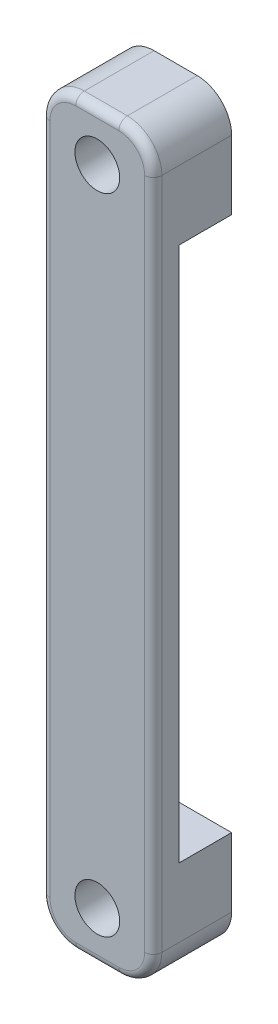
SolidWorks part; units mm, degrees
material "ABS"
ref_plane "Front Plane" through (0, 0, 0) normal (0, 0, 1) x (1, 0, 0)
ref_plane "Top Plane" through (0, 0, 0) normal (0, 1, 0) x (1, 0, 0)
ref_plane "Right Plane" through (0, 0, 0) normal (1, 0, 0) x (0, 0, -1)
sketch "Sketch1" plane through (0, 0, 0) normal (0, 0, 1) x (1, 0, 0)
  line L0 (-64.1444, 69.4911) -> (92.8306, 69.4911) construction
  line L1 (7.3028, 69.4911) -> (-5.6972, 69.4911)
  line L2 (7.3028, 69.4911) -> (7.3028, -18.6589)
  line L3 (7.3028, -18.6589) -> (-5.6972, -18.6589)
  line L4 (-5.6972, 69.4911) -> (-5.6972, -18.6589)
  line L5 (-5.6972, 68.4911) -> (7.3028, 68.4911)
  line L6 (-5.6972, -17.6589) -> (7.3028, -17.6589)
  line L7 (92.8306, -18.6589) -> (-64.1444, -18.6589) construction
  circle A0 centre (0.8028, 32.3036) radius 2.5 construction
  dimension "D1" = 4
  dimension "D2" = 4
  dimension "D3" = 1
  dimension "D4" = 1
extrude "Boss-Extrude1" add sketch "Sketch1" along normal blind 3 contours L4 L6 L2 L5 region at (0.8028, 25.4161, 0)
sketch "Sketch2" plane through (0, 0, 0) normal (0, 0, -1) x (-1, 0, 0)
  line L5 (-7.3028, 68.4911) -> (-7.3028, 56.4911)
  line L24 (-7.3028, 68.4911) -> (5.6972, 68.4911)
  line L25 (-7.3028, 56.4911) -> (5.6972, 56.4911)
  line L26 (5.6972, 68.4911) -> (5.6972, 56.4911)
  line L27 (-7.3028, 68.4911) -> (-7.3028, -17.6589) construction
  line L28 (5.6972, 68.4911) -> (5.6972, -17.6589) construction
  line L29 (-7.3028, 25.4161) -> (5.6972, 25.4161)
  line L30 (5.6972, -17.6589) -> (5.6972, -5.6589)
  line L31 (-7.3028, -5.6589) -> (5.6972, -5.6589)
  line L32 (-7.3028, -17.6589) -> (5.6972, -17.6589)
  line L33 (-7.3028, -17.6589) -> (-7.3028, -5.6589)
  circle A5 centre (-0.8028, 62.8036) radius 2.6
  circle A7 centre (-0.8028, -11.9714) radius 2.6
  dimension "D2" = 5.2
  dimension "D1" = 12
extrude "Boss-Extrude2" add sketch "Sketch2" along normal blind 6.1 contours L33 L32 L30 L31 A7 | L26 L24 L5 L25 A5
extrude "Cut-Extrude1" cut sketch "Sketch2<3>" against normal through all contours A5 | A7
sketch "Sketch2<3>" plane through (0, 0, 0) normal (0, 0, -1) x (-1, 0, 0) same geometry as "Sketch2"
fillet "Fillet3" radius 4 4 edges at (7.3028, -17.6589, -1.55) (-5.6972, -17.6589, -1.55) (7.3028, 68.4911, -1.55) (-5.6972, 68.4911, -1.55)
fillet "Fillet2" radius 1 8 edges at (-4.5256, -16.4874, 3) (-5.6972, 25.4161, 3) (-4.5256, 67.3195, 3) (0.8028, 68.4911, 3) (6.1312, 67.3195, 3) (7.3028, 25.4161, 3) (6.1312, -16.4874, 3) (0.8028, -17.6589, 3)
equation "\"D2@Sketch1\"=\"D1@Sketch1\""
